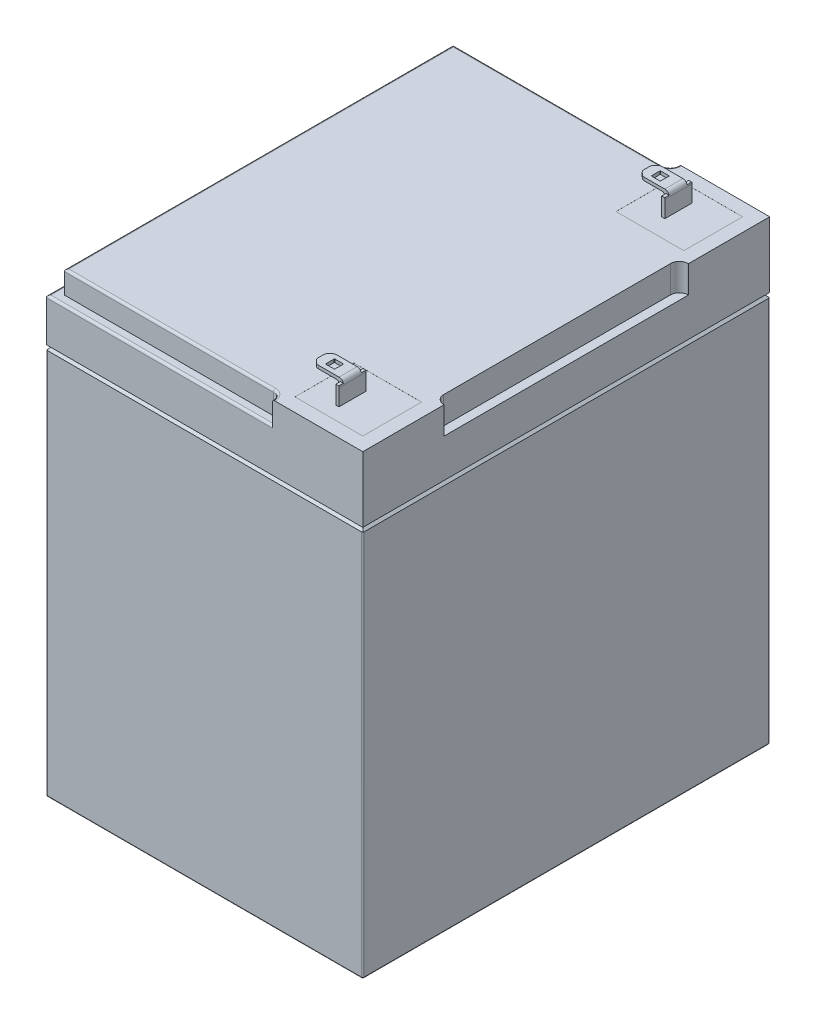
SolidWorks part; units mm, degrees
ref_plane "Front Plane" through (0, 0, 0) normal (0, 0, 1) x (1, 0, 0)
ref_plane "Top Plane" through (0, 0, 0) normal (0, 1, 0) x (1, 0, 0)
ref_plane "Right Plane" through (0, 0, 0) normal (1, 0, 0) x (0, 0, -1)
sketch "Sketch1" plane through (0, 0, 0) normal (0, 1, 0) x (1, 0, 0)
  line L1 (-35, 45) -> (35, 45)
  line L2 (-35, 45) -> (-35, -45)
  line L3 (-35, -45) -> (35, -45)
  line L4 (35, 45) -> (35, -45)
  line L5 (-35, 45) -> (35, -45) construction
  line L6 (-35, -45) -> (35, 45) construction
  point P0 (0, 0)
  dimension "D1" = 70
  dimension "D2" = 90
extrude "Boss-Extrude1" add sketch "Sketch1" along normal blind 86
chamfer "Chamfer1" distance 0.5 angle 45 4 edges at (-35, 86, 0) (0, 86, -45) (35, 86, 0) (0, 86, 45)
sketch "Sketch2" plane through (0, 86, 0) normal (0, 1, 0) x (1, 0, 0)
  line L1 (-35, 45) -> (35, 45)
  line L2 (-35, 45) -> (-35, -45)
  line L3 (-35, -45) -> (35, -45)
  line L4 (35, 45) -> (35, -45)
  line L5 (-35, 45) -> (35, -45) construction
  line L6 (-35, -45) -> (35, 45) construction
  point P0 (0, 0)
  dimension "D1" = 70
  dimension "D2" = 90
extrude "Boss-Extrude2" add sketch "Sketch2" along normal blind 15
chamfer "Chamfer2" distance 0.5 angle 45 4 edges at (-35, 86, 0) (0, 86, -45) (35, 86, 0) (0, 86, 45)
sketch "Sketch3" plane through (0, 101, 0) normal (0, 1, 0) x (1, 0, 0)
  line L4 (-35, -43) -> (35, -43)
  line L5 (-33, -43) -> (13.2, -43)
  line L7 (-33, 45) -> (-33, -45)
  line L8 (-33, 43) -> (-33, -43)
  line L10 (35, 43) -> (-35, 43)
  line L11 (13.2, 43) -> (-33, 43)
  line L12 (15, 45) -> (-35, 45)
  line L13 (15, -45) -> (15, 45)
  line L14 (15, -45) -> (15, -44.8)
  line L15 (-35, 45) -> (-35, -45)
  line L16 (-35, -45) -> (15, -45)
  line L17 (15, 44.8) -> (15, 45)
  arc A0 (13.2, -43) -> (15, -44.8) centre (13.2, -44.8) cw
  arc A1 (13.2, 43) -> (15, 44.8) centre (13.2, 44.8) ccw
  point P21 (15, 43)
  dimension "D5" = 1.8
  dimension "D6" = 1.8
  dimension "D2" = 2
  dimension "D1" = 2
  dimension "D3" = 2
  dimension "D4" = 20
extrude "Cut-Extrude1" cut sketch "Sketch3" against normal blind 5
fillet "Fillet1" radius 0.5 7 edges at (15, 101, -44.9) (14.4728, 101, -43.5272) (15, 101, 44.9) (14.4728, 101, 43.5272) (-9.9, 101, -43) (-33, 101, 0) (-9.9, 101, 43)
fillet "Fillet2" radius 0.5 3 edges at (-10, 96, -45) (-35, 96, 0) (-10, 96, 45)
sketch "Sketch5" plane through (0, 101, 0) normal (0, 1, 0) x (1, 0, 0)
  line L2 (15.5, -27) -> (35, -27)
  line L3 (34.9, -27) -> (35, -27)
  line L5 (35, 27) -> (15.5, 27)
  line L6 (35, 27) -> (34.9, 27)
  line L7 (35, 27) -> (35, -27)
  line L8 (33, -45) -> (33, 45)
  line L9 (33, -25.1) -> (33, 25.1)
  arc A0 (34.9, 27) -> (33, 25.1) centre (34.9, 25.1) ccw
  arc A1 (34.9, -27) -> (33, -25.1) centre (34.9, -25.1) cw
  dimension "D4" = 1.9
  dimension "D1" = 18
  dimension "D2" = 18
  dimension "D3" = 2
extrude "Cut-Extrude3" cut sketch "Sketch5" against normal blind 6
sketch "Sketch6" plane through (0, 101, 0) normal (0, 1, 0) x (1, 0, 0)
  line L2 (32, -45) -> (32, -27)
  line L3 (32, -42) -> (32, -29)
  line L4 (17, -42) -> (17, -29)
  line L5 (15.5, -42) -> (35, -42)
  line L6 (17, -42) -> (32, -42)
  line L7 (17, -29) -> (32, -29)
  line L9 (17, -42) -> (17, -27) construction
  line L10 (15.5, -29) -> (32, -29) construction
  line L11 (32, -42) -> (32, -27) construction
  line L12 (15.5, -42) -> (32, -42) construction
  line L14 (35, 42) -> (15.5, 42)
  line L15 (32, 42) -> (17, 42)
  line L16 (32, 29) -> (17, 29)
  line L17 (32, 27) -> (32, 45)
  line L18 (32, 29) -> (32, 42)
  line L19 (17, 29) -> (17, 42)
  line L21 (17, 27) -> (17, 45) construction
  line L22 (35, 29) -> (15.5, 29) construction
  line L23 (35, 42) -> (15.5, 42) construction
  line L24 (32, 27) -> (32, 45) construction
  dimension "D3" = 15
  dimension "D4" = 13
  dimension "D1" = 3
  dimension "D2" = 3
  dimension "D5" = 3
  dimension "D6" = 3
  dimension "D7" = 13
  dimension "D8" = 15
extrude "Cut-Extrude5" cut sketch "Sketch6" against normal blind 0.01
sketch "Sketch9" plane through (-0.7246, 100.99, 13.532) normal (0, 1, 0) x (1, 0, 0)
  line L3 (23.7919, -19.5) -> (23.7919, -25.5)
  line L5 (24.4919, -19.5) -> (24.4919, -25.5)
  line L8 (23.7919, -25.5) -> (24.4919, -25.5)
  line L9 (23.7919, -19.5) -> (24.4919, -19.5)
  line L11 (24.4919, -16) -> (24.4919, -29) construction
  line L12 (23.7919, -16) -> (23.7919, -29) construction
  point P4 (57, -25.5)
  point P5 (72, -25.5)
  point P6 (57, -22.5)
  point P7 (72, -22.5)
  point P8 (57, -19.5)
  point P9 (72, -19.5)
  dimension "D1" = 0.7
extrude "Boss-Extrude7" add sketch "Sketch9" along normal blind 4
sketch "Sketch11" plane through (-0.7246, 104.99, 13.532) normal (0, 1, 0) x (1, 0, 0)
  line L0 (24.4919, -24.4946) -> (18.9052, -24.4946)
  line L1 (24.4919, -20.4821) -> (24.4919, -24.4946)
  line L2 (24.4919, -25.5) -> (24.4919, -19.5) construction
  line L3 (18.9595, -20.4821) -> (24.4919, -20.4821)
  line L4 (17.4912, -21.9092) -> (17.4912, -23.0806)
  line L5 (19.5909, -21.495) -> (21.3907, -21.495)
  line L6 (21.3907, -23.4947) -> (19.5909, -23.4947)
  line L7 (19.4909, -21.9092) -> (19.4909, -23.0806)
  line L8 (17.8173, -21.1704) -> (18.2858, -20.7432)
  line L9 (17.784, -23.7876) -> (18.1982, -24.2017)
  line L10 (19.4909, -23.0806) -> (19.4909, -23.3947)
  line L12 (19.4909, -21.9092) -> (19.4909, -21.595)
  line L13 (21.4906, -21.9092) -> (21.4906, -23.0806)
  line L16 (21.4906, -21.595) -> (21.4906, -21.9092)
  line L17 (21.4906, -23.0806) -> (21.4906, -23.3947)
  arc A0 (18.9595, -20.4821) -> (18.2858, -20.7432) centre (18.9595, -21.482) ccw
  arc A1 (18.9052, -24.4946) -> (18.1982, -24.2017) centre (18.9052, -23.4947) cw
  arc A2 (17.4912, -23.0806) -> (17.784, -23.7876) centre (18.4911, -23.0806) ccw
  arc A3 (17.4912, -21.9092) -> (17.8173, -21.1704) centre (18.4911, -21.9092) cw
  arc A4 (19.4909, -23.3947) -> (19.5909, -23.4947) centre (19.5909, -23.3947) ccw
  arc A5 (21.4906, -23.3947) -> (21.3907, -23.4947) centre (21.3907, -23.3947) cw
  arc A6 (21.4906, -21.595) -> (21.3907, -21.495) centre (21.3907, -21.595) ccw
  arc A7 (19.4909, -21.595) -> (19.5909, -21.495) centre (19.5909, -21.595) cw
  point P1 (24.4919, -24.4946)
  point P3 (18.572, -20.4821)
  point P4 (14.9906, -20.5)
  point P5 (14.9906, -24.5)
  point P6 (18.4911, -24.4946)
  point P7 (17.4912, -21.4678)
  point P8 (24.4919, -20.4821)
  point P9 (24.4919, -22.5)
  point P20 (16.4048, -21.5)
  point P21 (21.9906, -21.5)
  point P22 (21.9906, -23.5)
  point P23 (16.4048, -23.5)
  dimension "D1" = 0.9999
  dimension "D7" = 0.1
extrude "Boss-Extrude9" add sketch "Sketch11" along normal blind 0.7
mirror "Mirror1" about plane through (0, 0, 0) normal (0, 0, 1) of "Boss-Extrude9", "Boss-Extrude7"
fillet "Fillet4" radius 1 2 edges at (23.7673, 105.69, -36.0204) (23.7673, 105.69, 36.0204)
fillet "Fillet5" radius 1 1 edges at (23.0673, 104.99, 36.0204)
fillet "Fillet6" radius 1 1 edges at (23.0673, 104.99, -36.0204)
fillet "Fillet8" radius 0.25 8 edges at (35, 42.75, -45) (35, 0, 0) (35, 42.75, 45) (-35, 42.75, 45) (0, 0, 45) (0, 0, -45) (-35, 0, 0) (-35, 42.75, -45)
